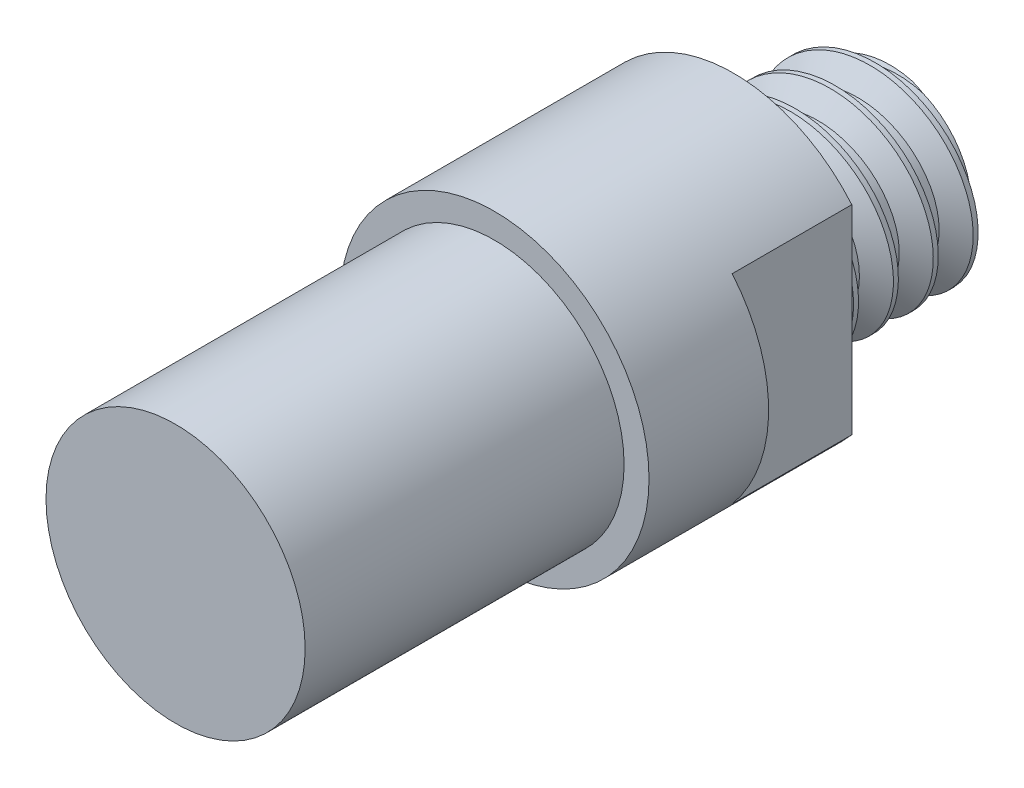
SolidWorks part; units mm, degrees
ref_plane "Front Plane" through (0, 0, 0) normal (1, 0, 0) x (0, 1, 0)
ref_plane "Top Plane" through (0, 0, 0) normal (0, 0, 1) x (0, 1, 0)
ref_plane "Right Plane" through (0, 0, 0) normal (0, 1, 0) x (-1, 0, 0)
sketch "Sketch1" plane through (0, 0, 0) normal (0, 0, 1) x (0, 1, 0)
  circle A0 centre (0, 0) radius 5
  dimension "D1" = 10
extrude "Boss-Extrude1" add sketch "Sketch1" along normal blind 8
thread "Thread1" pitch 2 method cut trim with end face yes profile "Thread Profile1" start angle 0, offset 3, length 13, pitch 2, diameter 10
ref_plane "Plane1" through (5, 0, -3) normal (0, -1, 0) x (1, 0, 0)
sketch "Thread Profile1" plane through (5, 0, -3) normal (0, -1, 0) x (1, 0, 0)
  line L0 (0, 0) -> (0, 2) construction
  line L11 (0, 0) -> (0, 1.75)
  line L12 (0, 1.75) -> (-1.0825, 1.125)
  line L13 (-1.0825, 1.125) -> (-1.0825, 0.625)
  line L15 (-1.0825, 0.625) -> (0, 0)
  line L17 (-1.0825, 0.875) -> (0, 0.875) construction
  point P2 (0, 0)
  dimension "Pitch" = 2
  dimension "Profile_Angle" = 60
  dimension "Profile_Land" = 0.5
  dimension "Profile_Height" = 1.0825
sketch "Sketch4" plane through (0, 0, 0) normal (0, 0, -1) x (1, 0, 0)
  circle A0 centre (0, 0) radius 4
  dimension "D1" = 8
extrude "Cut-Extrude1" cut sketch "Sketch4" against normal blind 10 draft 60 flip side to cut
sketch "Sketch5" plane through (0, 0, 8) normal (0, 0, 1) x (1, 0, 0)
  circle A0 centre (0, 0) radius 7.75
  dimension "D1" = 15.5
extrude "Boss-Extrude2" add sketch "Sketch5" along normal blind 12
sketch "Sketch6" plane through (0, 0, 20) normal (0, 0, 1) x (1, 0, 0)
  circle A0 centre (0, 0) radius 6.5
  dimension "D1" = 13
extrude "Boss-Extrude3" add sketch "Sketch6" along normal blind 16
sketch "Sketch7" plane through (0, 0, 8) normal (0, 0, -1) x (1, 0, 0)
  line L1 (-5.9214, -5) -> (5.9214, -5) construction
  line L2 (-5.9214, -5) -> (-5.9214, 5)
  line L3 (-5.9214, 5) -> (5.9214, 5) construction
  line L4 (5.9214, -5) -> (5.9214, 5)
  line L5 (-5.9214, -5) -> (5.9214, 5) construction
  line L6 (-5.9214, 5) -> (5.9214, -5) construction
  circle A1 centre (0, 0) radius 7.75 construction
  arc A2 (-5.9214, 5) -> (-5.9214, -5) centre (0, 0) ccw
  arc A3 (5.9214, 5) -> (-5.9214, 5) centre (0, 0) ccw construction
  arc A4 (-5.9214, -5) -> (5.9214, -5) centre (0, 0) ccw construction
  arc A5 (5.9214, -5) -> (5.9214, 5) centre (0, 0) ccw
  point P0 (0, 0)
  point P8 (0, 0)
  point P10 (0, 0)
  dimension "D1" = 10
extrude "Cut-Extrude2" cut sketch "Sketch7" against normal blind 6
